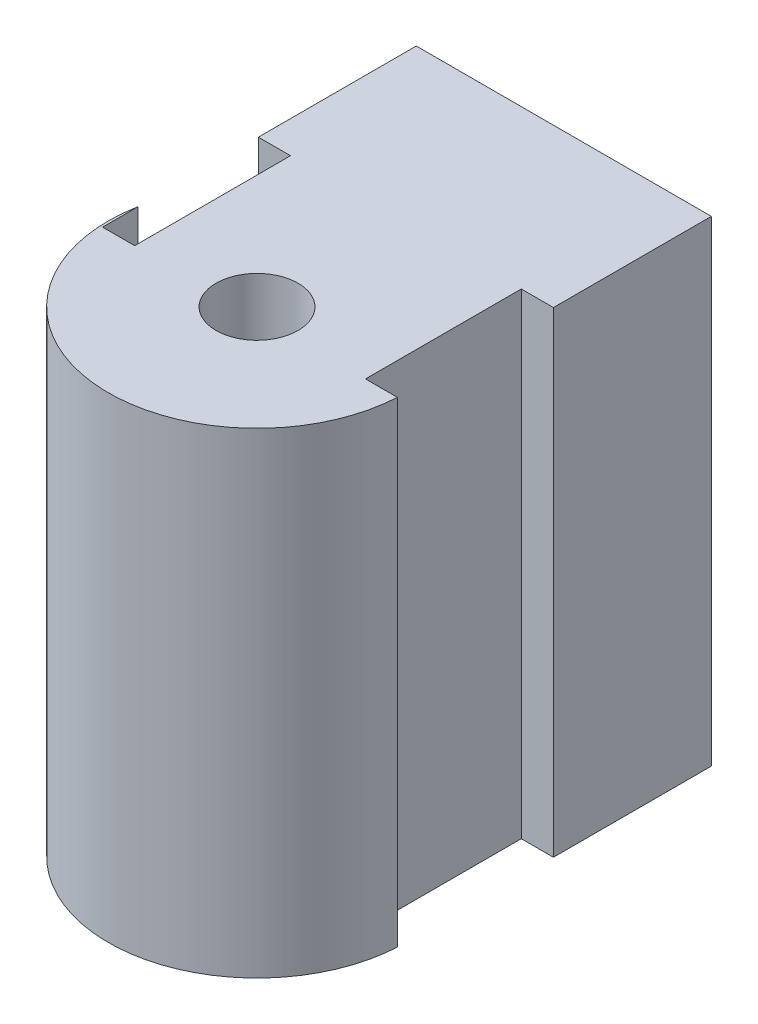
SolidWorks part; units mm, degrees
ref_plane "Front Plane" through (0, 0, 0) normal (0, 0, 1) x (1, 0, 0)
ref_plane "Top Plane" through (0, 0, 0) normal (0, 1, 0) x (1, 0, 0)
ref_plane "Right Plane" through (0, 0, 0) normal (1, 0, 0) x (0, 0, -1)
sketch "Sketch2" plane through (0, -2111.3899, 0) normal (0, 1, 0) x (1, 0, 0)
  circle A1 centre (-53.694, 163.8403) radius 12.7
extrude "Boss-Extrude6" add sketch "Sketch2" along normal blind 40.64
sketch "Sketch3" plane through (0, -2070.7499, 0) normal (0, 1, 0) x (1, 0, 0)
  circle A0 centre (-53.694, 163.8403) radius 3.5
  dimension "D1" = 7
extrude "Cut-Extrude1" cut sketch "Sketch3" against normal up to surface (40.64 mm away) up to face at (-66.394, -2111.3899, -163.8403)
sketch "Sketch4" plane through (0, -2111.3899, 0) normal (0, -1, 0) x (1, 0, 0)
  circle A0 centre (-61.9429, -159.0778) radius 1.778
  circle A2 centre (-53.694, -173.3653) radius 1.778
  circle A3 centre (-45.4451, -159.0778) radius 1.778
extrude "Cut-Extrude2" cut sketch "Sketch4" against normal blind 6
sketch "Sketch7" plane through (0, -2111.3899, 0) normal (0, -1, 0) x (1, 0, 0)
  line L9 (-40.994, -163.8403) -> (-40.994, -182.6343)
  line L10 (-40.994, -182.6343) -> (-66.1797, -182.6343)
  line L11 (-66.1797, -166.1636) -> (-66.1797, -182.6343)
  circle A0 centre (-53.694, -163.8403) radius 12.7 construction
  arc A1 (-66.1797, -166.1636) -> (-40.994, -163.8403) centre (-53.694, -163.8403) ccw
extrude "Boss-Extrude8" add sketch "Sketch7" against normal blind 10
sketch "Sketch8" plane through (0, 0, -182.6343) normal (0, 0, -1) x (-1, 0, 0)
  line L0 (40.994, -2101.3899) -> (40.994, -2111.3899) construction
  line L1 (40.994, -2101.3899) -> (66.1797, -2101.3899)
  line L2 (40.994, -2101.3899) -> (40.994, -2111.3899)
  line L3 (40.994, -2111.3899) -> (66.1797, -2111.3899)
  line L4 (66.1797, -2101.3899) -> (66.1797, -2111.3899)
  line L5 (66.1797, -2101.3899) -> (40.994, -2101.3899) construction
  line L6 (66.1797, -2111.3899) -> (40.994, -2111.3899) construction
  line L7 (66.1797, -2101.3899) -> (66.1797, -2111.3899) construction
extrude "Boss-Extrude9" add sketch "Sketch8" along normal up to surface (7.2848 mm away)
sketch "Sketch9" plane through (0, -2070.7499, 0) normal (0, 1, 0) x (1, 0, 0)
  line L0 (-40.994, 189.9191) -> (-40.994, 163.8403) construction
  line L2 (-66.1797, 163.8403) -> (-66.1797, 189.9191)
  line L3 (-66.1797, 189.9191) -> (-40.994, 189.9191)
  line L4 (-40.994, 163.8403) -> (-40.994, 189.9191)
  line L5 (-66.1797, 166.1636) -> (-66.1797, 189.9191) construction
  arc A0 (-40.994, 163.8403) -> (-66.1797, 163.8403) centre (-53.5868, 163.8403) ccw
extrude "Boss-Extrude10" add sketch "Sketch9" against normal up to surface (30.64 mm away) up to face at (-53.322, -2101.3899, -180.3317)
hole_wizard "CSK for M3 Flat Head Machine Screw1" positions "Sketch14" profile "Sketch15" countersink size "M3" standard "ANSI Metric"
sketch "Sketch14" plane through (0, 0, -189.9191) normal (0, 0, -1) x (-1, 0, 0)
  point P10 (53.5868, -2075.7499)
  point P12 (62.6264, -2075.7499)
  point P14 (44.5473, -2075.7499)
sketch "Sketch15" plane through (-53.5868, -2075.7499, -189.9191) normal (1, 0, 0) x (0, 1, 0)
  line L0 (0, 0) -> (0, 10)
  line L1 (0, 10) -> (1.7, 8.9785)
  line L2 (1.7, 8.9785) -> (1.7, 1.45)
  line L3 (1.7, 1.45) -> (3.15, 0)
  line L5 (3.15, 0) -> (0, 0)
  line L6 (-1.7, 1.45) -> (-3.15, 0) construction
  line L10 (0, 10) -> (-1.7, 8.9785) construction
  line L11 (0, -6.35) -> (0, 107.95) construction
  dimension "Hole Dia." = 3.4
  dimension "Hole Depth" = 10
  dimension "Near C'Sink Dia." = 6.3
  dimension "Near C'Sink Angle" = 90
  dimension "Drill Angle" = 118
ref_plane "Plane1" through (0, -2091.0699, 0) normal (0, 1, 0) x (1, 0, 0)
mirror "Mirror1" about plane through (0, -2091.0699, 0) normal (0, 1, 0) of "CSK for M3 Flat Head Machine Screw1"
sketch "Sketch16" plane through (0, -2070.7499, 0) normal (0, 1, 0) x (1, 0, 0)
  line L0 (-53.694, 151.1403) -> (-53.694, 163.1403) construction
  line L1 (-53.694, 151.1403) -> (-61.6485, 151.1403) construction
  line L2 (-57.6712, 151.1403) -> (-57.6712, 176.4403) construction
  line L3 (-53.694, 163.1403) -> (-66.3747, 163.1403) construction
  line L4 (-66.1797, 189.9191) -> (-66.1797, 166.1636) construction
  line L5 (-66.1797, 176.4403) -> (-63.4359, 176.4403)
  line L6 (-66.1797, 176.4403) -> (-66.1797, 163.1403)
  line L7 (-66.1797, 163.1403) -> (-63.4359, 163.1403)
  line L8 (-63.4359, 176.4403) -> (-63.4359, 163.1403)
  line L9 (-40.994, 163.8403) -> (-40.994, 189.9191) construction
  line L11 (-53.5868, 189.9191) -> (-53.5868, 168.4351) construction
  line L12 (-40.994, 189.9191) -> (-66.1797, 189.9191) construction
  line L13 (-53.4797, 163.1403) -> (-40.799, 163.1403) construction
  line L14 (-43.7377, 176.4403) -> (-43.7377, 163.1403)
  line L15 (-40.994, 163.1403) -> (-43.7377, 163.1403)
  line L16 (-40.994, 176.4403) -> (-40.994, 163.1403)
  line L17 (-40.994, 176.4403) -> (-43.7377, 176.4403)
  arc A0 (-66.1797, 166.1636) -> (-40.994, 163.8403) centre (-53.694, 163.8403) ccw construction
  dimension "D1" = 12
  dimension "D2" = 25.3
  dimension "D3" = 16.6773
  dimension "D4" = 22.4419
extrude "Cut-Extrude3" cut sketch "Sketch16" against normal through all
